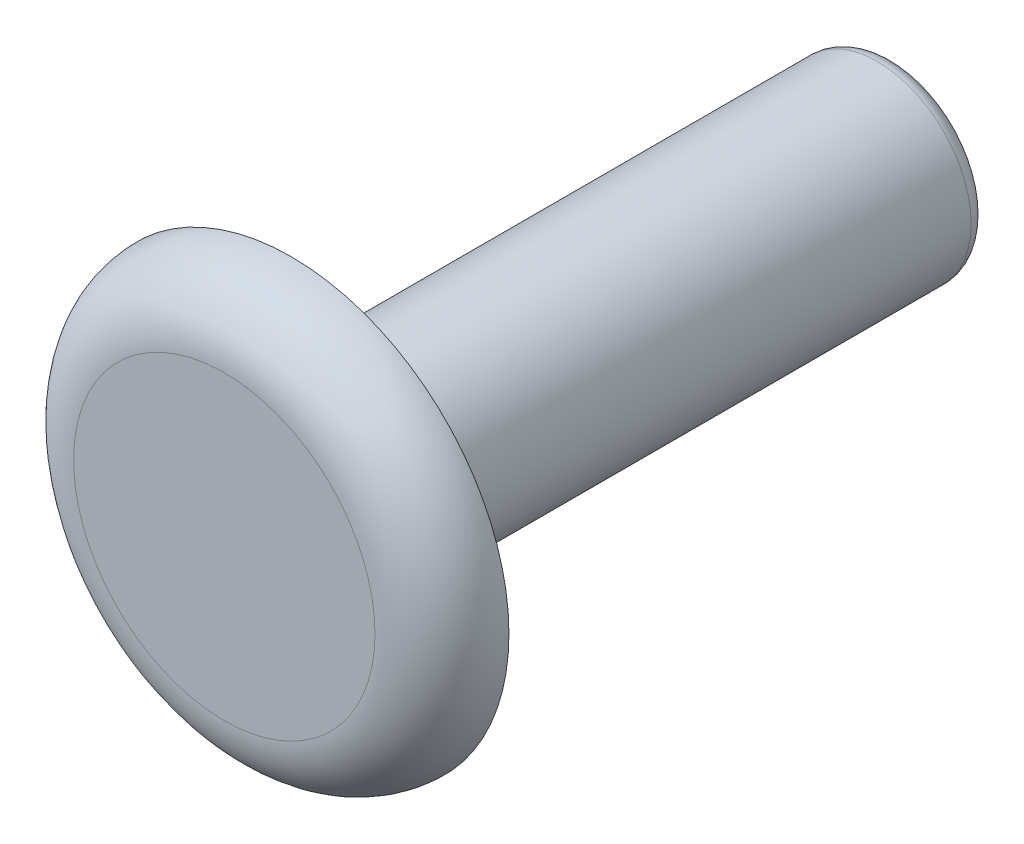
SolidWorks part; units mm, degrees
ref_plane "Front Plane" through (0, 0, 0) normal (0, 0, 1) x (1, 0, 0)
ref_plane "Top Plane" through (0, 0, 0) normal (0, 1, 0) x (1, 0, 0)
ref_plane "Right Plane" through (0, 0, 0) normal (1, 0, 0) x (0, 0, -1)
sketch "Esquisse1" plane through (0, 0, 0) normal (0, 0, 1) x (1, 0, 0)
  circle A0 centre (-28.0683, 21.8847) radius 1.4
  dimension "D1" = 2.8
extrude "Boss.-Extru.1" add sketch "Esquisse1" along normal blind 9
sketch "Esquisse2" plane through (0, 0, 9) normal (0, 0, 1) x (1, 0, 0)
  circle A0 centre (-28.0683, 21.8847) radius 3.25
  dimension "D1" = 6.5
extrude "Boss.-Extru.2" add sketch "Esquisse2" along normal blind 1
fillet "Congé1" radius 1 1 edges at (-24.8183, 21.8847, 10)
fillet "Congé2" radius 0.25 1 edges at (-26.6683, 21.8847, 0)
